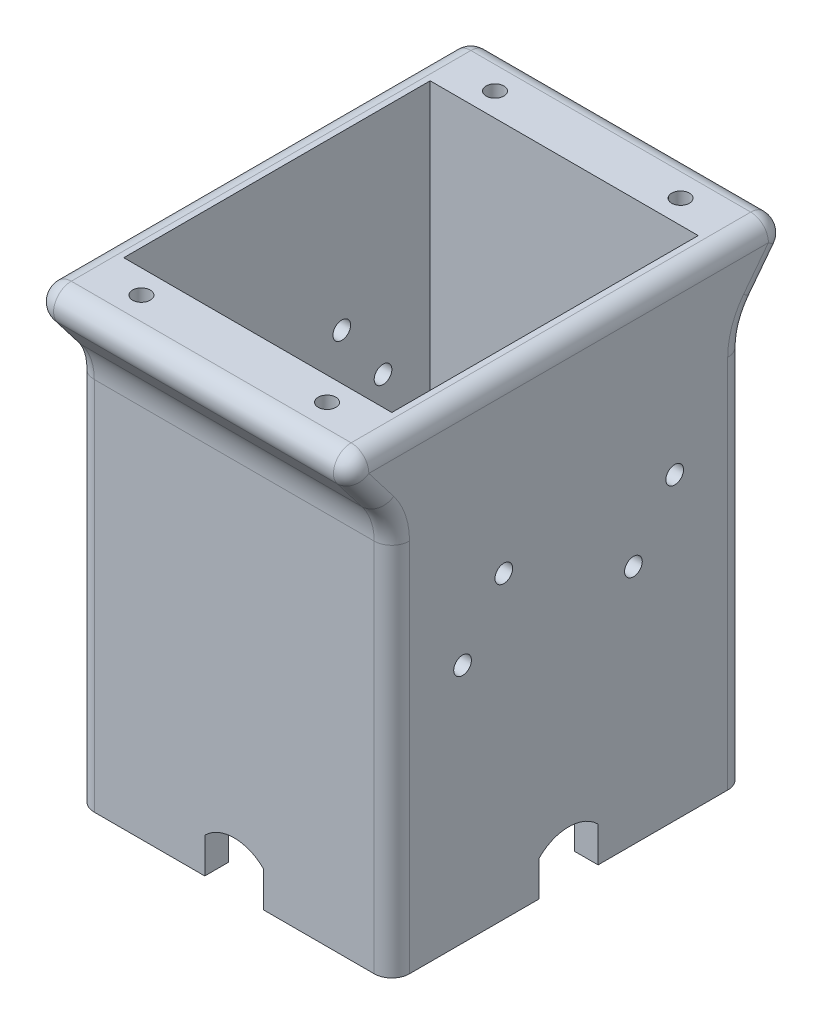
SolidWorks part; units mm, degrees
ref_plane "Front Plane" through (0, 0, 0) normal (0, 0, 1) x (1, 0, 0)
ref_plane "Top Plane" through (0, 0, 0) normal (0, 1, 0) x (1, 0, 0)
ref_plane "Right Plane" through (0, 0, 0) normal (1, 0, 0) x (0, 0, -1)
sketch "Sketch1" plane through (0, 0, 0) normal (0, 1, 0) x (1, 0, 0)
  line L1 (-26.75, 30) -> (26.75, 30)
  line L2 (-26.75, 30) -> (-26.75, -30)
  line L3 (-26.75, -30) -> (26.75, -30)
  line L4 (26.75, 30) -> (26.75, -30)
  line L5 (-26.75, 30) -> (26.75, -30) construction
  line L6 (-26.75, -30) -> (26.75, 30) construction
  line L7 (-22.75, 26) -> (22.75, 26)
  line L8 (-22.75, 26) -> (-22.75, -26)
  line L9 (-22.75, -26) -> (22.75, -26)
  line L10 (22.75, 26) -> (22.75, -26)
  line L11 (-22.75, 26) -> (22.75, -26) construction
  line L12 (-22.75, -26) -> (22.75, 26) construction
  point P0 (0, 0)
  point P6 (0, 0)
  dimension "D1" = 45.5
  dimension "D2" = 4
  dimension "D3" = 4
extrude "Boss-Extrude1" add sketch "Sketch1" along normal blind 80
sketch "Sketch3" plane through (-26.75, 0, 0) normal (-1, 0, 0) x (0, 0, 1)
  line L0 (-30, 80) -> (30, 80) construction
  circle A0 centre (18, 50.85) radius 1.5
  circle A1 centre (11, 40.85) radius 1.5
  dimension "D1" = 3
  dimension "D3" = 3
  dimension "D2" = 29.15
  dimension "D4" = 10
  dimension "D5" = 7
  dimension "D6" = 8
extrude "Cut-Extrude1" cut sketch "Sketch3" against normal blind 4 and the other way through all
pattern_linear "LPattern1" count 2 spacing 29 along (0, 0, -1) of "Cut-Extrude1"
sketch "Sketch4" plane through (26.75, 0, 0) normal (1, 0, 0) x (0, 0, -1)
  line L0 (-30, 80) -> (30, 80) construction
  circle A0 centre (-11, 50.85) radius 1.5
  circle A1 centre (-18, 40.85) radius 1.5
  dimension "D1" = 3
  dimension "D2" = 3
  dimension "D3" = 10
  dimension "D4" = 7
  dimension "D5" = 29.15
  dimension "D6" = 8
extrude "Cut-Extrude2" cut sketch "Sketch4" against normal blind 4
pattern_linear "LPattern2" count 2 spacing 29 along (0, 0, -1) of "Cut-Extrude2"
sketch "Sketch5" plane through (-26.75, 0, 0) normal (-1, 0, 0) x (0, 0, 1)
  line L0 (30, 80) -> (30, 67)
  line L1 (30, 80) -> (30, 0) construction
  line L2 (30, 67) -> (40, 80)
  line L3 (40, 80) -> (30, 80)
  line L4 (-30, 80) -> (-30, 67)
  line L5 (-30, 80) -> (-30, 0) construction
  line L6 (-30, 67) -> (-40, 80)
  line L7 (-30, 80) -> (-40, 80)
  dimension "D1" = 10
  dimension "D2" = 13
extrude "Boss-Extrude2" add sketch "Sketch5" against normal through all
fillet "Fillet1" radius 10 2 edges at (0, 67, 30) (0, 67, -30)
fillet "Fillet2" radius 3 16 edges at (26.75, 31.7994, -30) (26.75, 66.8188, -30.5326) (26.75, 74.8479, -36.0369) (26.75, 80, 0) (0, 80, -40) (26.75, 31.7994, 30) (26.75, 66.8188, 30.5326) (-26.75, 31.7994, 30) (-26.75, 66.8188, 30.5326) (-26.75, 31.7994, -30) (-26.75, 66.8188, -30.5326) (26.75, 74.8479, 36.0369) (0, 80, 40) (-26.75, 74.8479, 36.0369) (-26.75, 74.8479, -36.0369) (-26.75, 80, 0)
sketch "Sketch6" plane through (0, 80, 0) normal (0, 1, 0) x (1, 0, 0)
  line L0 (-22.75, -26) -> (22.75, -26) construction
  line L2 (-23.75, 33.9074) -> (-23.75, -33.9074) construction
  line L3 (0, -33.9074) -> (0, -26) construction
  line L4 (-23.75, -33.9074) -> (23.75, -33.9074) construction
  circle A0 centre (-15.75, -30) radius 1.5
  circle A1 centre (15.75, -30) radius 1.5
  dimension "D2" = 3
  dimension "D1" = 4
  dimension "D3" = 8
extrude "Cut-Extrude3" cut sketch "Sketch6" against normal blind 9
ref_plane "Plane1" through (0, 0, 0) normal (0, 0, 1) x (1, 0, 0)
mirror "Mirror1" about plane through (0, 0, 0) normal (0, 0, 1) of "Cut-Extrude3"
sketch "Sketch7" plane through (26.75, 0, 0) normal (1, 0, 0) x (0, 0, -1)
  line L0 (5, 0) -> (5, 6)
  line L1 (-27, 0) -> (27, 0) construction
  line L2 (-5, 0) -> (-5, 6)
  line L3 (5, 0) -> (-5, 0)
  arc A0 (-5, 6) -> (5, 6) centre (0, 1.101) cw
  dimension "D5" = 7
  dimension "D1" = 6
  dimension "D2" = 6
  dimension "D3" = 5
  dimension "D4" = 5
extrude "Cut-Extrude4" cut sketch "Sketch7" against normal through all
sketch "Sketch8" plane through (0, 0, -30) normal (0, 0, -1) x (-1, 0, 0)
  line L0 (5, 0) -> (5, 6)
  line L1 (-23.75, 0) -> (23.75, 0) construction
  line L2 (-5, 0) -> (-5, 6)
  line L3 (5, 0) -> (-5, 0)
  arc A0 (-5, 6) -> (5, 6) centre (0, 1.101) cw
  dimension "D5" = 7
  dimension "D1" = 6
  dimension "D2" = 6
  dimension "D3" = 5
  dimension "D4" = 5
extrude "Cut-Extrude5" cut sketch "Sketch8" against normal through all
